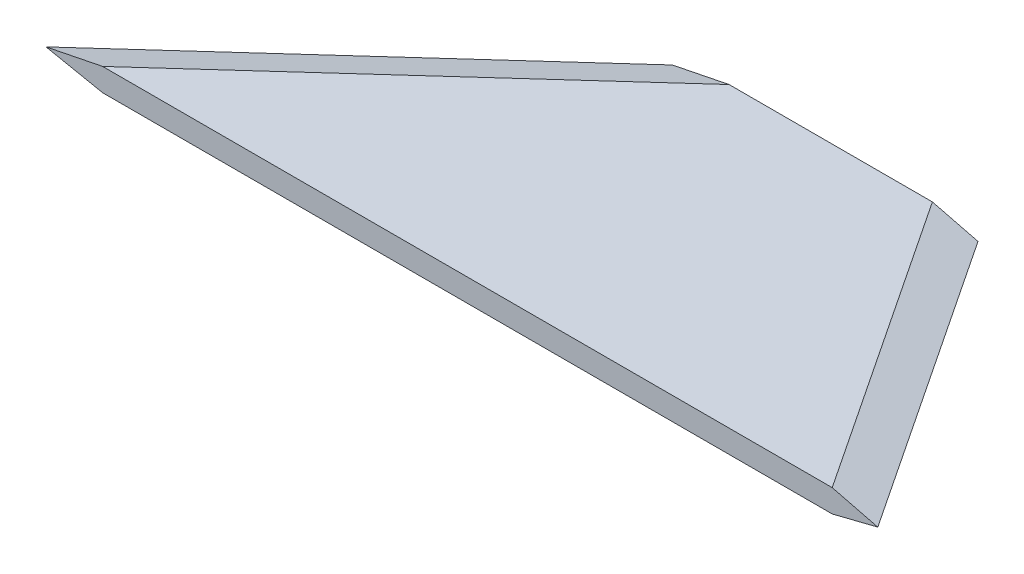
SolidWorks part; units mm, degrees
ref_plane "Front Plane" through (0, 0, 0) normal (0, 0, 1) x (1, 0, 0)
ref_plane "Top Plane" through (0, 0, 0) normal (0, 1, 0) x (1, 0, 0)
ref_plane "Right Plane" through (0, 0, 0) normal (1, 0, 0) x (0, 0, -1)
sketch "Sketch1" plane through (0, 0, 0) normal (0, 1, 0) x (1, 0, 0)
  line L0 (0, 0) -> (203.2, 0)
  line L1 (203.2, 0) -> (157.48, 68.9356)
  line L2 (157.48, 68.9356) -> (76.2, 68.9356)
  line L3 (76.2, 68.9356) -> (0, 0)
  dimension "D1" = 203.2
  dimension "D2" = 81.28
  dimension "D3" = 68.9356
  dimension "D4" = 76.2
extrude "Fin Cut" add sketch "Sketch1" along normal blind 5.2832
chamfer "Chamfer1" distance 3.81 distance2 12.7 1 edges at (180.34, 5.2832, -34.4678) first distance on face at (180.34, 2.6416, -34.4678)
chamfer "Chamfer2" distance 12.7 distance2 3.81 1 edges at (180.34, 0, -34.4678) first distance on face at (109.22, 0, -34.4678)
chamfer "Chamfer3" distance 3.81 distance2 12.7 1 edges at (38.1, 5.2832, -34.4678) first distance on face at (38.1, 2.6416, -34.4678)
chamfer "Chamfer4" distance 12.7 distance2 3.81 1 edges at (38.1, 0, -34.4678) first distance on face at (101.6003, 0, -34.4678)
